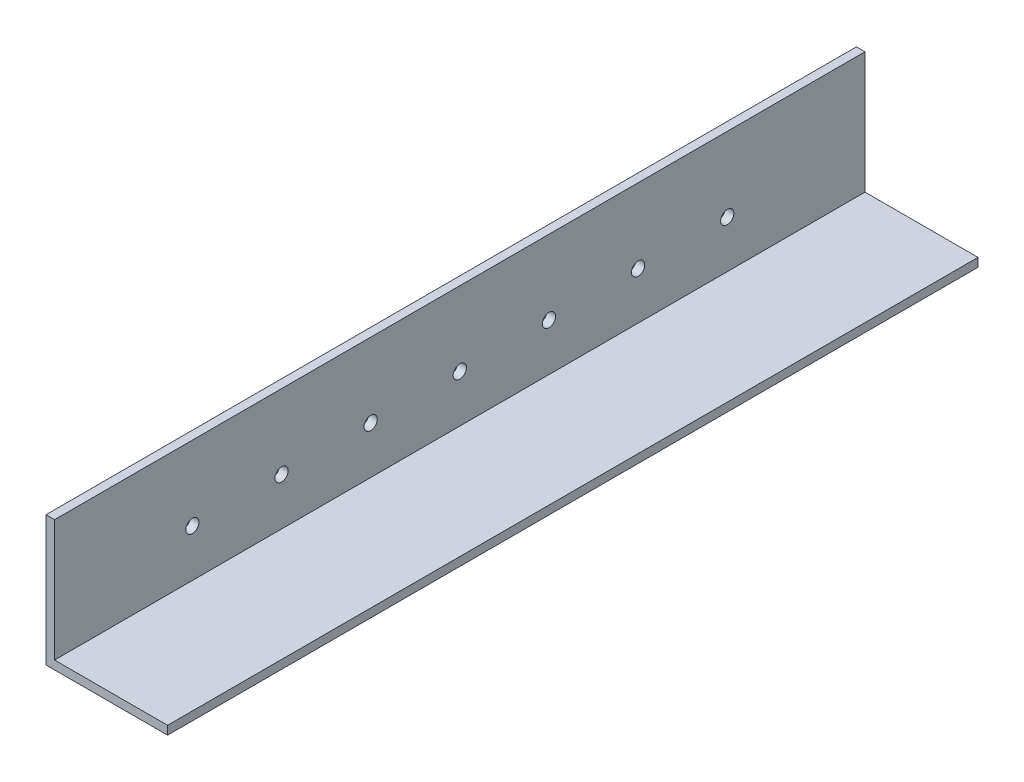
SolidWorks part; units mm, degrees
ref_plane "Alzado" through (0, 0, 0) normal (0, 0, 1) x (1, 0, 0)
ref_plane "Planta" through (0, 0, 0) normal (0, 1, 0) x (1, 0, 0)
ref_plane "Vista lateral" through (0, 0, 0) normal (1, 0, 0) x (0, 0, -1)
sketch "Croquis1" plane through (0, 0, 0) normal (0, 0, 1) x (1, 0, 0)
  line L0 (-19.325, 0) -> (0, 0) construction
  line L1 (22.5, -25.675) -> (-22.5, -25.675)
  line L2 (22.5, -25.675) -> (22.5, -22.5)
  line L3 (22.5, -22.5) -> (-22.5, -22.5)
  line L4 (-22.5, -25.675) -> (-22.5, -22.5)
  line L5 (-22.5, -22.5) -> (-19.325, -22.5)
  line L6 (-22.5, -22.5) -> (-22.5, 22.5)
  line L7 (-22.5, 22.5) -> (-19.325, 22.5)
  line L8 (-19.325, -22.5) -> (-19.325, 22.5)
  line L9 (0, 0) -> (0, -22.5) construction
  dimension "D1" = 3.175
  dimension "D2" = 3.175
  dimension "D3" = 45
  dimension "D4" = 45
extrude "Saliente-Extruir1" add sketch "Croquis1" along normal mid plane 300 contours L3 L8 L7 L6 | L4 L1 L2 L3 region at (0, -24.0875, 0) region at (-20.9125, 0, 0)
sketch "Croquis2" plane through (0, 0, 0) normal (1, 0, 0) x (0, 0, -1)
  line L0 (-185.7724, -5) -> (180.2818, -5) construction
  line L1 (0, 9.483) -> (0, -16.9346) construction
  line L2 (-152.7724, -5) -> (213.2818, -5) construction
  line L3 (-119.7724, -5) -> (246.2818, -5) construction
  line L4 (-86.7724, -5) -> (279.2818, -5) construction
  line L17 (-185.7724, -1.287) -> (180.2818, -1.287) construction
  line L18 (-152.7724, -1.287) -> (213.2818, -1.287) construction
  line L19 (-119.7724, -1.287) -> (246.2818, -1.287) construction
  line L20 (-218.7724, -1.287) -> (147.2818, -1.287) construction
  line L21 (-218.7724, 2.426) -> (147.2818, 2.426) construction
  line L22 (-185.7724, 2.426) -> (180.2818, 2.426) construction
  line L23 (-152.7724, 2.426) -> (213.2818, 2.426) construction
  line L24 (-251.7724, 2.426) -> (114.2818, 2.426) construction
  line L25 (-251.7724, 6.1391) -> (114.2818, 6.1391) construction
  line L26 (-218.7724, 6.1391) -> (147.2818, 6.1391) construction
  line L27 (-185.7724, 6.1391) -> (180.2818, 6.1391) construction
  line L28 (-284.7724, 6.1391) -> (81.2818, 6.1391) construction
  circle A0 centre (0, -5) radius 2.45
  circle A1 centre (33, -5) radius 2.45
  circle A2 centre (66, -5) radius 2.45
  circle A3 centre (99, -5) radius 2.45
  circle A16 centre (-66, 2.426) radius 2.45 [skipped]
  circle A17 centre (-33, 2.426) radius 2.45 [skipped]
  circle A18 centre (-33, -1.287) radius 2.45 [skipped]
  circle A19 centre (-33, 6.1391) radius 2.45 [skipped]
  circle A20 centre (-66, 6.1391) radius 2.45 [skipped]
  circle A21 centre (0, 6.1391) radius 2.45 [skipped]
  circle A22 centre (0, 2.426) radius 2.45 [skipped]
  circle A23 centre (0, -1.287) radius 2.45 [skipped]
  circle A24 centre (33, 2.426) radius 2.45 [skipped]
  circle A25 centre (33, -1.287) radius 2.45 [skipped]
  circle A26 centre (-99, 6.1391) radius 2.45 [skipped]
  circle A27 centre (66, -1.287) radius 2.45 [skipped]
  circle A28 centre (-99, -5) radius 2.45
  circle A29 centre (-66, -5) radius 2.45
  circle A30 centre (-33, -5) radius 2.45
  point P8 (-33, 2.426)
  point P9 (0, 0)
  point P21 (0, 0)
  point P22 (0, 0)
  dimension "D2" = 4.9
  dimension "D1" = 5
  dimension "D5" = 33
  dimension "D3" = 4
  dimension "D4" = 4
extrude "Cortar-Extruir1" cut sketch "Croquis2" against normal blind 50
